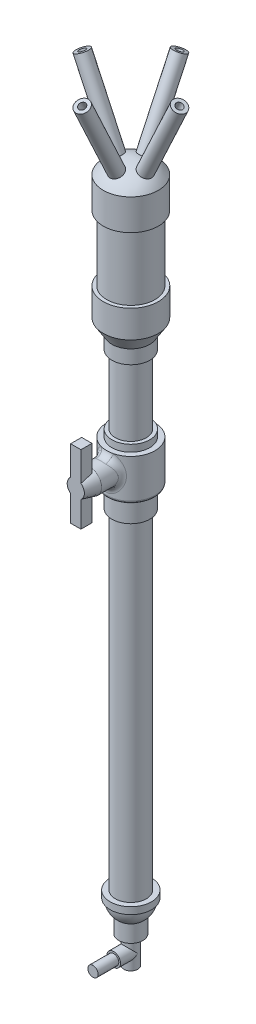
SolidWorks part; units mm, degrees
ref_plane "Front Plane" through (0, 0, 0) normal (0, 0, 1) x (1, 0, 0)
ref_plane "Top Plane" through (0, 0, 0) normal (0, 1, 0) x (1, 0, 0)
ref_plane "Right Plane" through (0, 0, 0) normal (1, 0, 0) x (0, 0, -1)
sketch "Sketch2" plane through (0, 0, 0) normal (1, 0, 0) x (0, 0, -1)
  line L0 (25.4, 0) -> (89.807, 138.1213) construction
  line L1 (25.4, 0) -> (25.4, 11.7751) construction
  dimension "D1" = 25.4
  dimension "D2" = 25
  dimension "D3" = 152.4
ref_plane "Plane1" through (0, 138.1213, -89.807) normal (0, 0.9063, -0.4226) x (1, 0, 0)
sketch "Sketch3" plane through (0, 138.1213, -89.807) normal (0, 0.9063, -0.4226) x (1, 0, 0)
  circle A0 centre (0, 0) radius 6.35
  circle A1 centre (0, 0) radius 12.7
  dimension "D1" = 12.7
  dimension "D2" = 25.4
extrude "Boss-Extrude1" add sketch "Sketch3" against normal up to vertex (152.4 mm away) up to point (0, 0, -25.4)
sketch "Sketch4" plane through (0, 0, 0) normal (0, 0, 1) x (1, 0, 0)
  line L0 (0, 0) -> (0, 9.525) construction
  line L1 (0, 9.525) -> (0, -73.025)
  line L3 (50.8, -15.875) -> (50.8, -73.025)
  line L4 (50.8, -73.025) -> (0, -73.025)
  spline S0 degree 2 poles (0, 9.525) (33.493, 9.9892) (50.8, -15.875) knots 0 0 0 1 1 1
  dimension "D1" = 9.525
  dimension "D2" = 50.8
  dimension "D3" = 25.4
  dimension "D4" = 82.55
revolve "Revolve1" add sketch "Sketch4" angle 360 about L0
pattern_circular "CirPattern1" count 4 over 360 about axis through (0, 0, 0) along (0, -1, 0) of "Boss-Extrude1"
sketch "Sketch5" plane through (0, -73.025, 0) normal (0, -1, 0) x (1, 0, 0)
  circle A0 centre (0, 0) radius 44.45
  dimension "D1" = 88.9
extrude "Boss-Extrude2" add sketch "Sketch5" along normal blind 120.65
sketch "Sketch6" plane through (0, 0, 0) normal (0, 0, 1) x (1, 0, 0)
  line L1 (0, -193.675) -> (0, -295.275)
  line L2 (-44.45, -193.675) -> (44.45, -193.675) construction
  line L3 (0, -295.275) -> (34.925, -295.275)
  line L4 (34.925, -295.275) -> (34.925, -269.875)
  line L5 (34.925, -269.875) -> (50.8, -244.475)
  line L6 (50.8, -244.475) -> (50.8, -193.675)
  line L7 (50.8, -193.675) -> (0, -193.675)
  dimension "D1" = 50.8
  dimension "D2" = 50.8
  dimension "D3" = 101.6
  dimension "D4" = 34.925
  dimension "D5" = 25.4
revolve "Revolve2" add sketch "Sketch6" angle 360 about L1
sketch "Sketch7" plane through (0, -295.275, 0) normal (0, -1, 0) x (1, 0, 0)
  circle A0 centre (0, 0) radius 28.575
  dimension "D1" = 57.15
extrude "Boss-Extrude3" add sketch "Sketch7" along normal blind 127
sketch "Sketch8" plane through (0, 0, 0) normal (0, 0, 1) x (1, 0, 0)
  line L0 (0, -422.275) -> (0, -549.275)
  line L1 (-28.575, -422.275) -> (28.575, -422.275) construction
  line L2 (0, -549.275) -> (34.925, -549.275)
  line L3 (34.925, -549.275) -> (34.925, -511.175)
  line L4 (34.925, -511.175) -> (44.45, -511.175)
  line L5 (44.45, -511.175) -> (44.45, -434.975)
  line L6 (44.45, -434.975) -> (34.925, -434.975)
  line L7 (34.925, -434.975) -> (34.925, -422.275)
  line L8 (34.925, -422.275) -> (0, -422.275)
  dimension "D1" = 127
  dimension "D2" = 44.45
  dimension "D3" = 34.925
  dimension "D4" = 12.7
  dimension "D5" = 34.925
  dimension "D6" = 38.1
revolve "Revolve3" add sketch "Sketch8" angle 360 about L0
fillet "Fillet1" radius 4.7625 2 edges at (-34.925, -511.175, 0) (-44.45, -511.175, 0)
sketch "Sketch9" plane through (0, -549.275, 0) normal (0, -1, 0) x (1, 0, 0)
  circle A0 centre (0, 0) radius 28.575
  dimension "D1" = 57.15
extrude "Boss-Extrude4" add sketch "Sketch9" along normal blind 609.6
sketch "Sketch10" plane through (0, 0, 0) normal (0, 0, 1) x (1, 0, 0)
  line L0 (0, -1158.875) -> (0, -1228.725)
  line L1 (-28.575, -1158.875) -> (28.575, -1158.875) construction
  line L2 (0, -1228.725) -> (-22.225, -1228.725)
  line L3 (-22.225, -1228.725) -> (-22.225, -1197.6418)
  line L4 (0, -1158.875) -> (-38.1, -1158.875)
  line L5 (-38.1, -1158.875) -> (-38.1, -1171.575)
  line L6 (-38.1, -1171.575) -> (-34.925, -1171.575)
  arc A0 (-34.925, -1171.575) -> (-22.225, -1197.6418) centre (0, -1170.6863) ccw
  point P12 (-14.639, -1205.1316)
  point P13 (-22.225, -1197.6418)
  point P14 (-22.225, -1198.2432)
  dimension "D1" = 12.7
  dimension "D2" = 69.85
  dimension "D3" = 38.1
  dimension "D4" = 34.925
  dimension "D5" = 22.225
revolve "Revolve4" add sketch "Sketch10" angle 360 about L0
sketch "Sketch11" plane through (0, -1228.725, 0) normal (0, -1, 0) x (1, 0, 0)
  circle A0 centre (0, 0) radius 12.7
  dimension "D1" = 25.4
extrude "Boss-Extrude5" add sketch "Sketch11" along normal blind 50.8
sketch "Sketch12" plane through (0, 0, 0) normal (0, 0, 1) x (1, 0, 0)
  line L0 (-12.7, -1228.725) -> (12.7, -1228.725) construction
  circle A0 centre (0, -1254.125) radius 12.7
  dimension "D1" = 25.4
  dimension "D2" = 25.4
extrude "Boss-Extrude6" add sketch "Sketch12" along normal blind 31.75
sketch "Sketch13" plane through (0, 0, 31.75) normal (0, 0, 1) x (1, 0, 0)
  circle A0 centre (0, -1254.125) radius 9.525
  dimension "D1" = 19.05
extrude "Boss-Extrude7" add sketch "Sketch13" along normal blind 38.1
sketch "Sketch14" plane through (0, 0, 0) normal (0, 0, 1) x (1, 0, 0)
  line L0 (44.45, -434.975) -> (-44.45, -434.975) construction
  circle A0 centre (0, -466.725) radius 22.225
  dimension "D1" = 44.45
  dimension "D2" = 31.75
extrude "Boss-Extrude8" add sketch "Sketch14" along normal blind 76.2
sketch "Sketch15" plane through (0, 0, 0) normal (1, 0, 0) x (0, 0, -1)
  line L0 (-76.2, -466.725) -> (-101.6, -466.725)
  line L1 (-76.2, -444.5) -> (-76.2, -488.95) construction
  line L2 (-101.6, -466.725) -> (-101.6, -450.85)
  line L3 (-101.6, -450.85) -> (-76.2, -444.5)
  line L4 (-76.2, -444.5) -> (-76.2, -466.725)
  dimension "D1" = 15.875
  dimension "D2" = 25.4
revolve "Revolve5" add sketch "Sketch15" angle 360 about L0
sketch "Sketch16" plane through (0, 0, 0) normal (1, 0, 0) x (0, 0, -1)
  line L1 (-101.6, -400.05) -> (-81.28, -400.05)
  line L2 (-101.6, -400.05) -> (-101.6, -527.05)
  line L3 (-101.6, -527.05) -> (-81.28, -527.05)
  line L4 (-81.28, -400.05) -> (-81.28, -527.05)
  line L5 (44.45, -434.975) -> (-44.45, -434.975) construction
  line L6 (-101.6, -450.85) -> (-101.6, -482.6) construction
  dimension "D1" = 20.32
  dimension "D2" = 127
  dimension "D3" = 34.925
  dimension "D4" = 0
extrude "Boss-Extrude9" add sketch "Sketch16" along normal mid plane 19.05
fillet "Fillet2" radius 12.7 1 edges at (22.0979, -464.3515, 38.5679)
